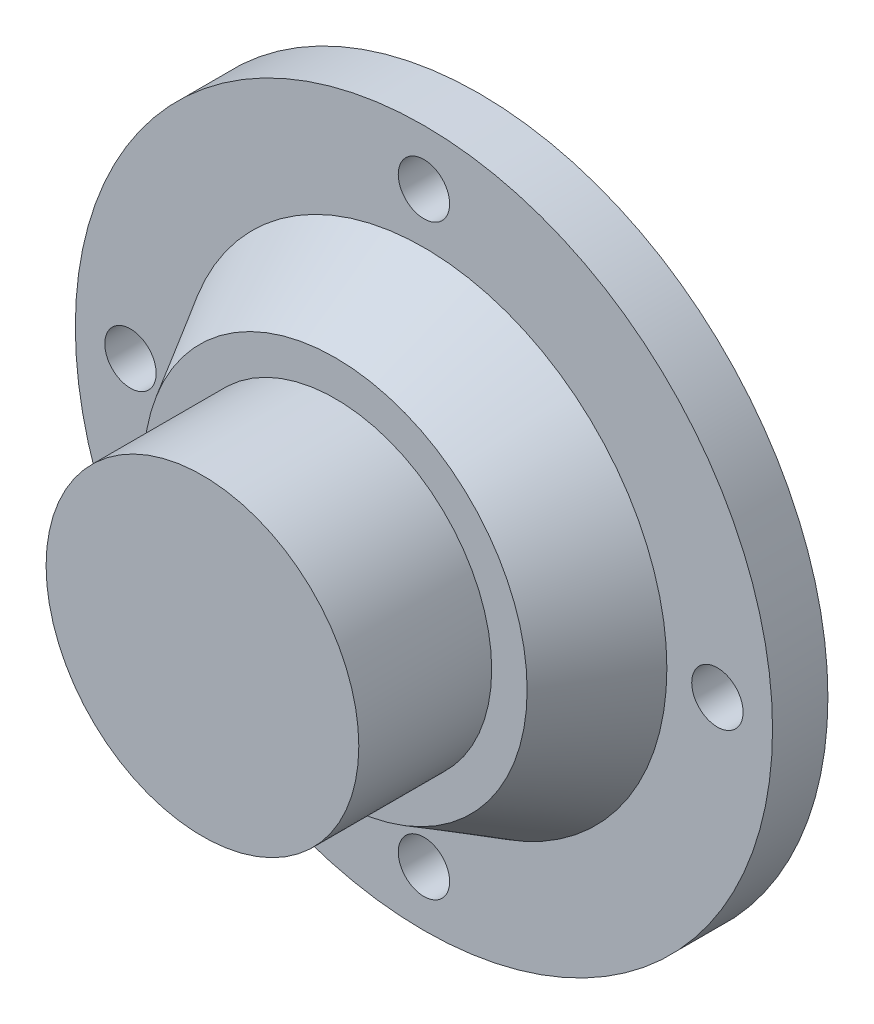
SolidWorks part; units mm, degrees
ref_plane "Front Plane" through (0, 0, 0) normal (0, 0, 1) x (1, 0, 0)
ref_plane "Top Plane" through (0, 0, 0) normal (0, 1, 0) x (1, 0, 0)
ref_plane "Right Plane" through (0, 0, 0) normal (1, 0, 0) x (0, 0, -1)
sketch "Sketch2" plane through (0, 0, 0) normal (1, 0, 0) x (0, 0, -1)
  line L0 (0, 0) -> (15.875, 0)
  line L1 (15.875, 0) -> (15.875, 17.2807)
  line L3 (7.62, 10.9982) -> (7.62, 8.9662)
  line L4 (7.62, 8.9662) -> (0, 8.9662)
  line L5 (0, 0) -> (0, 8.9662)
  line L7 (12.7, 13.9311) -> (7.62, 10.9982)
  line L8 (12.7, 13.9311) -> (12.7, 19.9898)
  line L9 (12.7, 19.9898) -> (15.875, 19.9898)
  line L10 (15.875, 19.9898) -> (15.875, 17.2807)
  dimension "D1" = 19.9898
  dimension "D2" = 12.7
  dimension "D3" = 3.175
  dimension "D4" = 10.9982
  dimension "D5" = 120
  dimension "D6" = 5.08
  dimension "D7" = 2.032
revolve "Revolve1" add sketch "Sketch2" angle 360 about L0
sketch "Sketch3" plane through (0, 0, -15.875) normal (0, 0, -1) x (-1, 0, 0)
  line L0 (-16.8275, 0) -> (16.8275, 0) construction
  line L1 (0, -16.8275) -> (0, 16.8275) construction
  circle A0 centre (0, 0) radius 16.8275 construction
  point P3 (-16.8275, 0)
  point P4 (16.8275, 0)
  point P5 (0, -16.8275)
  point P6 (0, 16.8275)
  dimension "D1" = 33.655
hole_wizard "#4 Clearance Hole1" positions "Sketch3" profile "Sketch4" hole size "#4" standard "ANSI Inch" end condition through all
sketch "Sketch4" plane through (0, 16.8275, -15.875) normal (1, 0, 0) x (0, 1, 0)
  line L0 (0, 0) -> (0, 15.875)
  line L1 (0, 15.875) -> (1.4732, 15.875)
  line L2 (1.4732, 15.875) -> (1.4732, 0)
  line L5 (1.4732, 0) -> (0, 0)
  line L11 (0, -6.35) -> (0, 107.95) construction
  dimension "Thru Hole Dia." = 2.9464
  dimension "Thru Hole Depth" = 15.875
